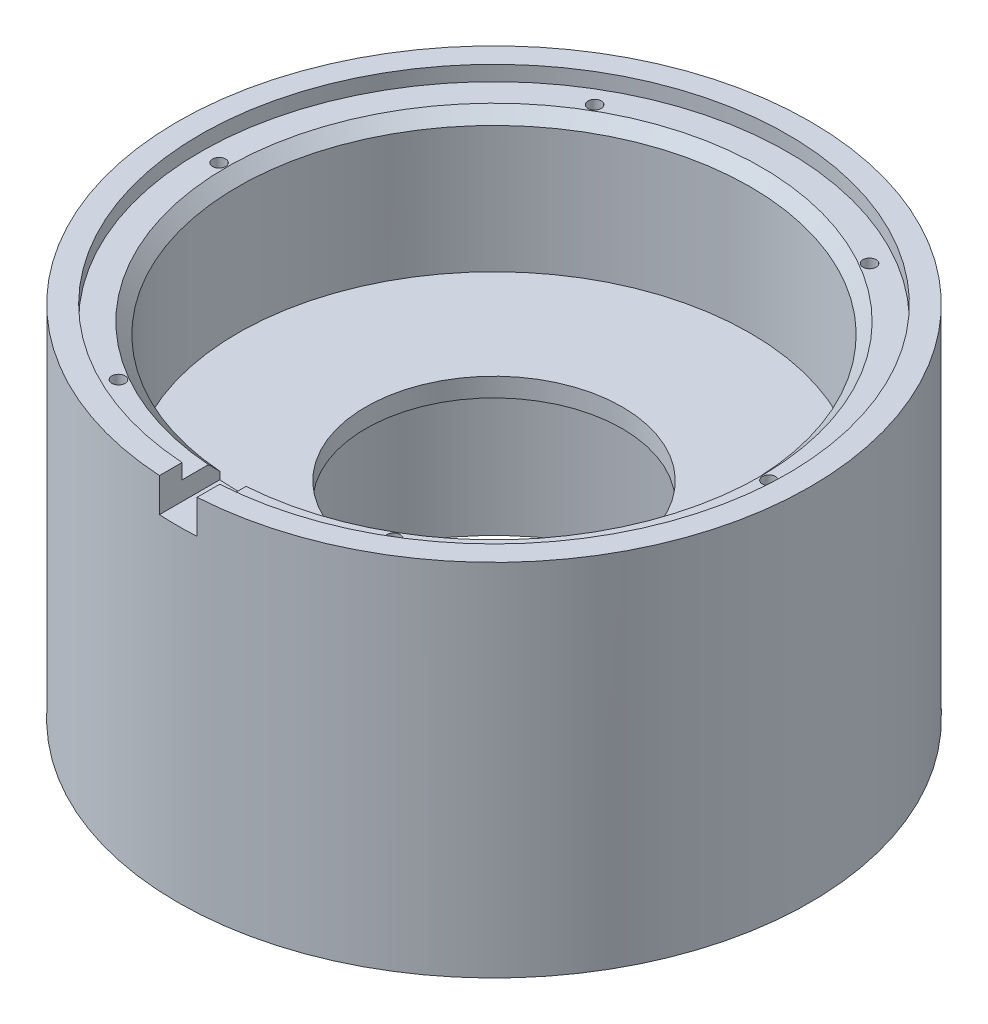
SolidWorks part; units mm, degrees
material "1060 Alloy"
ref_plane "Front Plane" through (0, 0, 0) normal (0, 0, 1) x (1, 0, 0)
ref_plane "Top Plane" through (0, 0, 0) normal (0, 1, 0) x (1, 0, 0)
ref_plane "Right Plane" through (0, 0, 0) normal (1, 0, 0) x (0, 0, -1)
sketch "Sketch7" plane through (0, 0, 0) normal (0, 0, 1) x (1, 0, 0)
  line L0 (0, -30.2319) -> (0, 30.2319) construction
  line L1 (-42.0375, 21.59) -> (-39.0375, 21.59)
  line L2 (-39.0375, 21.59) -> (-39.0375, 19.59)
  line L3 (-39.0375, 19.59) -> (-34.0375, 19.59)
  line L4 (-34.0375, 19.59) -> (-34.0375, 1.25)
  line L5 (-30, -1.25) -> (-17.0375, -1.25)
  line L6 (-17.0375, -1.25) -> (-17.0375, 1.25)
  line L7 (-17.0375, 1.25) -> (-34.0375, 1.25)
  line L8 (-30, -1.25) -> (-30, -26.25)
  line L9 (-30, -26.25) -> (-42.0375, -26.25)
  line L10 (-42.0375, -26.25) -> (-42.0375, 21.59)
  line L11 (-17.0375, 0) -> (0, 0) construction
  point P4 (0, 0)
  point P20 (-36.5375, 19.59)
  dimension "D1" = 3
  dimension "D2" = 2
  dimension "D3" = 5
  dimension "D4" = 34.0375
  dimension "D7" = 2.5
  dimension "D8" = 17
  dimension "D6" = 25
  dimension "D9" = 30
  dimension "D5" = 18.34
revolve "Base Motor Housing" add sketch "Sketch7" angle 360 about L0
sketch "Sketch8" plane through (0, 21.59, 0) normal (0, 1, 0) x (1, 0, 0)
  line L0 (0, 0) -> (0, -42.0375) construction
  line L1 (-2.5, -42.0375) -> (2.5, -42.0375)
  line L2 (-2.5, -42.0375) -> (-2.5, -33.9456)
  line L3 (-2.5, -33.9456) -> (2.5, -33.9456)
  line L4 (2.5, -42.0375) -> (2.5, -33.9456)
  circle A0 centre (0, 0) radius 42.0375 construction
  circle A1 centre (0, 0) radius 34.0375 construction
  point P10 (0, -42.0375)
  dimension "D1" = 5
extrude "Wire Hole" cut sketch "Sketch8" against normal offset from surface (4.5 mm away) 2.5 up to face at (0, 19.59, -39.0375)
sketch "Sketch9" plane through (0, 19.59, 0) normal (0, 1, 0) x (1, 0, 0)
  circle A0 centre (0, 0) radius 34.0375 construction
  circle A1 centre (0, 0) radius 34.0375 construction
  circle A2 centre (0, 0) radius 36.5375 construction
  circle A3 centre (-36.5375, 0) radius 0.875
  circle A4 centre (-18.2687, 31.6424) radius 0.875
  circle A5 centre (18.2688, 31.6424) radius 0.875
  circle A6 centre (36.5375, 0) radius 0.875
  circle A7 centre (18.2687, -31.6424) radius 0.875
  circle A8 centre (-18.2688, -31.6424) radius 0.875
  point P21 (0, 0)
  dimension "D2" = 1.75
  dimension "D1" = 2.5
  dimension "D3" = 6
extrude "Cut-Extrude4" cut sketch "Sketch9" against normal blind 6
sketch "Sketch10" plane through (0, -26.25, 0) normal (0, -1, 0) x (1, 0, 0)
  line L0 (-30, 0) -> (-42.0375, 0) construction
  circle A0 centre (0, 0) radius 30 construction
  circle A1 centre (0, 0) radius 30 construction
  circle A2 centre (0, 0) radius 42.0375 construction
  circle A3 centre (0, 0) radius 42.0375 construction
  circle A4 centre (-36.0187, 0) radius 2.875
  circle A5 centre (-18.0094, 31.1932) radius 2.875
  circle A6 centre (18.0094, 31.1932) radius 2.875
  circle A7 centre (36.0187, 0) radius 2.875
  circle A8 centre (18.0094, -31.1932) radius 2.875
  circle A9 centre (-18.0094, -31.1932) radius 2.875
  circle A10 centre (0, 0) radius 36.0187 construction
  point P22 (0, 0)
  dimension "D1" = 5.75
  dimension "D2" = 6
extrude "Cut-Extrude5" cut sketch "Sketch10" against normal blind 20
chamfer "Chamfer1" distance 1.5 angle 45 1 edges at (0, 19.59, -34.0375)
equation "\"D2@Sketch9\"=\"Back_mount_hole\""
equation "\"Stator_OD\"= 68'No Tolerance given"
equation "\"D4@Sketch7\"= 1 / 2 * \"Stator_OD\" + \"Stator_Gap\""
equation "\"A\"=18.34"
equation "\"Rotor_ID\"= 34'No Tolerance Given"
equation "\"bearing_Thickness\"= 20'Currently non-sense"
equation "\"D8@Sketch7\"=1/2*(\"Stator_OD\"-\"Rotor_ID\")"
equation "\"D6@Sketch7\"=\"bearing_Thickness\"+5"
equation "\"bearing_OD\"= 60'currently non-sense"
equation "\"D9@Sketch7\"=\"bearing_OD\"*1/2"
equation "\"D5@Sketch7\"=\"A\""
equation "\"Stator_Gap\"= 0.0375'+- 0.0125 (From 1.3.3.1 Kollmorgen manual)"
equation "\"Back_mount_hole\"= 1.75'To be tapped to M2 (USE LOCKTITE)"
equation "\"D1@Cut-Extrude5\"=\"bearing_Thickness\""
equation "\"facePlate_Mount_Hole\"= 5.75'To be tapped to M6"
equation "\"D1@Sketch10\"=\"facePlate_Mount_Hole\""
equation "\"final_shaftD\"= 8'NEMA 23 shaft diameter. Should fit with harmonic?"
equation "\"bearing_ID\"= 40'Random number"
